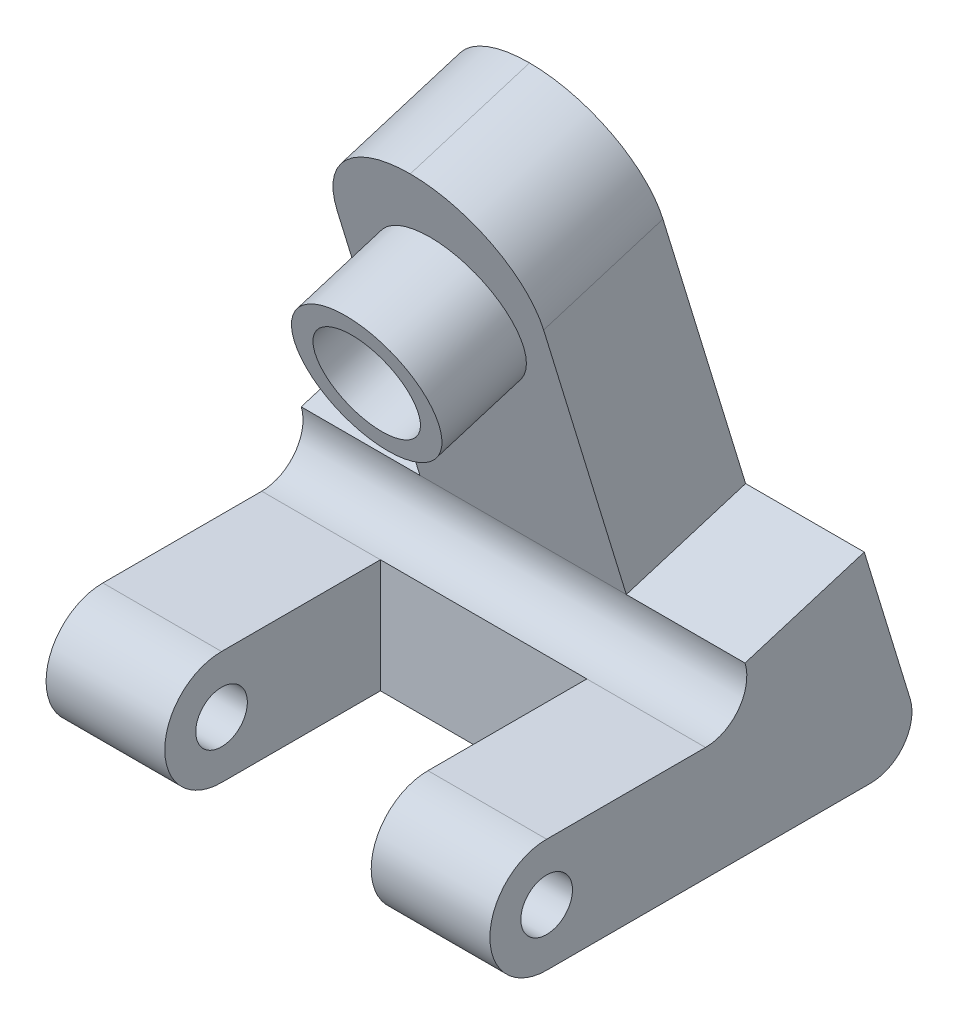
SolidWorks part; units mm, degrees
ref_plane "Front Plane" through (0, 0, 0) normal (0, 0, 1) x (1, 0, 0)
ref_plane "Top Plane" through (0, 0, 0) normal (0, 1, 0) x (1, 0, 0)
ref_plane "Right Plane" through (0, 0, 0) normal (1, 0, 0) x (0, 0, -1)
sketch "Sketch1" plane through (0, 0, 0) normal (1, 0, 0) x (0, 0, -1)
  line L5 (0, 0) -> (-25.4, 0) construction
  line L6 (-4.2676, 14.0808) -> (-35.8448, 4.4267) construction
  line L7 (-35.8448, 4.4267) -> (-33.2373, 4.4267) construction
  line L8 (-25.4, 0) -> (-25.4, 7.62) construction
  line L9 (-4.2676, 14.0808) -> (13.95, 19.6505) construction
  line L10 (0, 3.4925) -> (13.208, 3.4925)
  line L11 (0, -3.4925) -> (23.368, -3.4925)
  line L12 (13.208, 3.4925) -> (5.2614, 29.4846)
  line L13 (23.368, -3.4925) -> (12.6, 31.7282)
  line L14 (12.6, 31.7282) -> (5.2614, 29.4846)
  circle A2 centre (0, 0) radius 1.5875
  arc A3 (0, 3.4925) -> (0, -3.4925) centre (0, 0) ccw
  dimension "D1" = 25.4
  dimension "D2" = 17
  dimension "D7" = 3.175
  dimension "D8" = 6.985
  dimension "D3" = 10.922
  dimension "D4" = 33.02
  dimension "D5" = 7.62
  dimension "D6" = 19.05
  dimension "D9" = 7.6738
  dimension "D10" = 23.368
  dimension "D11" = 36.83
extrude "Boss-Extrude1" add sketch "Sketch1" along normal blind 27.305
fillet "Fillet1" radius 2.54 2 edges at (13.6525, 3.4925, -13.208) (13.6525, -3.4925, -23.368)
sketch "Sketch2" plane through (0, 0, 0) normal (0, 0, 1) x (1, 0, 0)
  line L0 (0, 18.1299) -> (27.305, 18.1299) construction
  line L1 (0, 29.4846) -> (0, 6.7751) construction
  line L2 (27.305, 29.4846) -> (27.305, 6.7751) construction
  line L3 (13.6525, 6.7751) -> (13.6525, -3.4925) construction
  line L4 (7.3025, 6.7751) -> (20.0025, 6.7751)
  line L5 (7.3025, 6.7751) -> (7.3025, -3.4925)
  line L6 (7.3025, -3.4925) -> (20.0025, -3.4925)
  line L7 (20.0025, 6.7751) -> (20.0025, -3.4925)
  line L8 (0, 6.7751) -> (27.305, 6.7751) construction
  line L9 (27.305, -3.4925) -> (0, -3.4925) construction
  dimension "D1" = 12.7
  dimension "D2" = 7.3025
extrude "Cut-Extrude1" cut sketch "Sketch2" against normal up to surface and the other way through all up to face at (13.6525, 18.1299, -8.7329)
sketch "Sketch3" plane through (0, 3.9915, -13.0555) normal (0, -0.2924, 0.9563) x (1, 0, 0)
  line L0 (13.6525, 9.4503) -> (13.6525, 26.658) construction
  line L2 (27.305, 26.658) -> (0, 26.658) construction
  line L3 (0, 9.4503) -> (27.305, 9.4503) construction
  line L4 (0, -10.172) -> (0, 26.658) construction
  line L5 (27.305, 26.658) -> (27.305, 2.9109) construction
  line L6 (0, 9.4503) -> (0, 26.658) construction
  line L7 (0, 18.0541) -> (27.305, 18.0541) construction
  circle A0 centre (13.6525, 18.0541) radius 4.445
  circle A1 centre (13.6525, 18.0541) radius 3.175
  point P2 (0, 0)
  dimension "D1" = 8.89
  dimension "D2" = 6.35
  dimension "D3" = 8.6038
extrude "Boss-Extrude2" add sketch "Sketch3" along normal up to vertex (5.4337 mm away)
sketch "Sketch4" plane through (0, 3.9915, -13.0555) normal (0, -0.2924, 0.9563) x (1, 0, 0)
  circle A0 centre (13.6525, 18.0541) radius 3.4925
extrude "Cut-Extrude2" cut sketch "Sketch4" against normal up to surface (7.6738 mm away) up to face at (13.6525, 15.7592, -17.4822)
sketch "Sketch5" plane through (0, 0, 0) normal (-1, 0, 0) x (0, 0, 1)
  line L0 (-12.6, 31.7282) -> (-5.2614, 29.4846)
  line L1 (-5.2614, 29.4846) -> (-12.2044, 6.7751)
  line L2 (-12.2044, 6.7751) -> (-19.5429, 9.0187)
  line L3 (-22.3644, -0.2099) -> (-12.6, 31.7282) construction
  line L4 (-19.5429, 9.0187) -> (-12.6, 31.7282)
extrude "Cut-Extrude3" cut sketch "Sketch5" against normal up to surface (7.3025 mm away) up to face at (7.3025, 0, 1.5875)
sketch "Sketch6" plane through (27.305, 0, 0) normal (1, 0, 0) x (0, 0, -1)
  line L0 (12.6, 31.7282) -> (5.2614, 29.4846)
  line L1 (5.2614, 29.4846) -> (12.2044, 6.7751)
  line L2 (12.2044, 6.7751) -> (19.5429, 9.0187)
  line L3 (19.5429, 9.0187) -> (12.6, 31.7282)
extrude "Cut-Extrude4" cut sketch "Sketch6" against normal up to surface (7.3025 mm away) up to face at (20.0025, 0, -1.5875)
sketch "Sketch7" plane through (20.0025, 0, 0) normal (-1, 0, 0) x (0, 0, 1)
  line L0 (-9.7754, 3.4925) -> (-9.7754, -3.4925)
  line L1 (-15.3435, -3.4925) -> (0, -3.4925) construction
  line L2 (-9.7754, -3.4925) -> (-15.3435, -3.4925)
  line L3 (-15.3435, -3.4925) -> (-12.2044, 6.7751)
  arc A0 (-12.2044, 6.7751) -> (-9.7754, 3.4925) centre (-9.7754, 6.0325) ccw construction
  arc A1 (-12.2044, 6.7751) -> (-9.7754, 3.4925) centre (-9.7754, 6.0325) ccw
extrude "Boss-Extrude3" add sketch "Sketch7" along normal up to surface (12.7 mm away) up to face at (7.3025, 0, 1.5875)
fillet "Fillet2" radius 6.35 2 edges at (20.0025, 30.6064, -8.9307) (7.3025, 30.6064, -8.9307)
